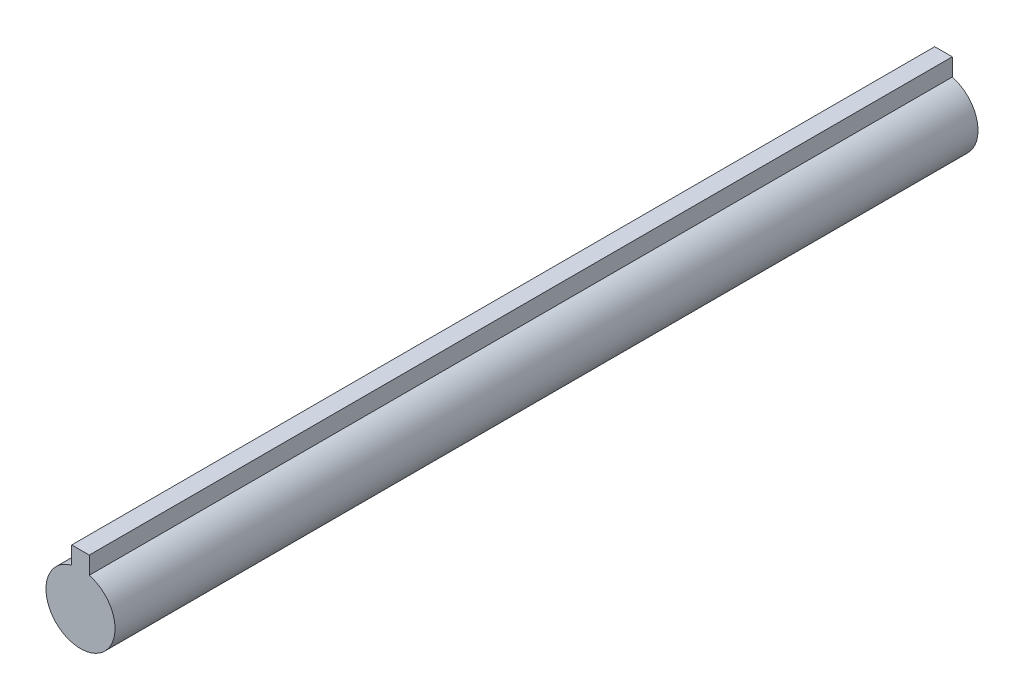
SolidWorks part; units mm, degrees
ref_plane "Front Plane" through (0, 0, 0) normal (0, 0, 1) x (1, 0, 0)
ref_plane "Top Plane" through (0, 0, 0) normal (0, 1, 0) x (1, 0, 0)
ref_plane "Right Plane" through (0, 0, 0) normal (1, 0, 0) x (0, 0, -1)
sketch "Sketch1" plane through (0, 0, 0) normal (0, 0, 1) x (1, 0, 0)
  line L0 (-0.254, 0.9672) -> (0.254, 0.9672)
  line L1 (-0.254, 0.9672) -> (-0.254, 1.4752)
  line L2 (0.254, 0.9672) -> (0.254, 1.4752)
  line L3 (-0.254, 1.4752) -> (0.254, 1.4752)
  circle A0 centre (0, 0) radius 1
  dimension "D1" = 2
  dimension "D2" = 0.508
  dimension "D3" = 0.508
extrude "Boss-Extrude1" add sketch "Sketch1" along normal mid plane 25 contours L0 A0 | A0 L2 L3 L1 | L0 L2 L3 L1 region at (0, 1.2321, 0) region at (0, -0.0035, 0)
